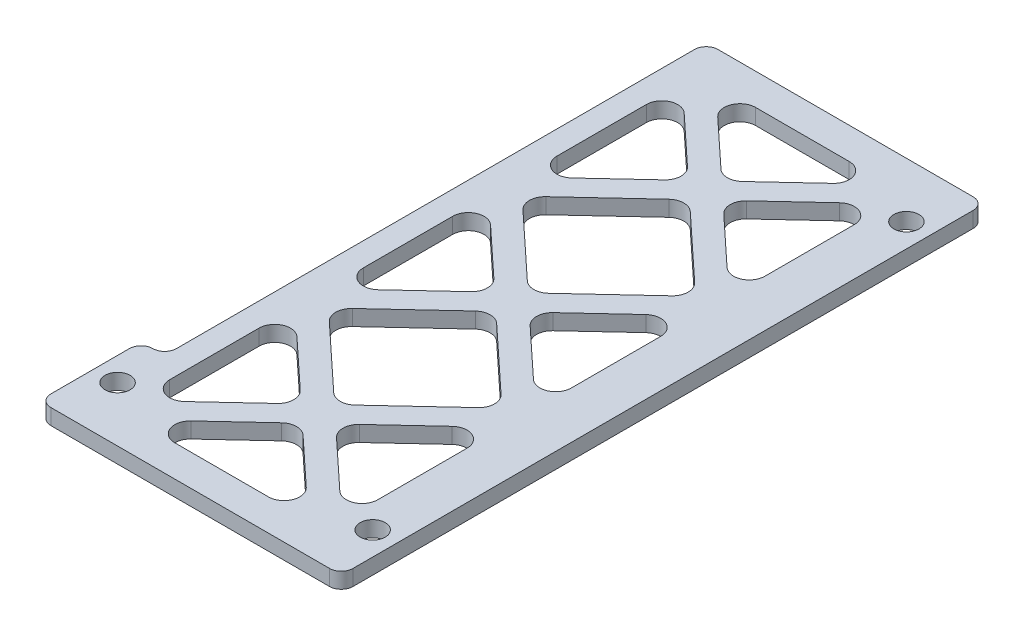
SolidWorks part; units mm, degrees
material "Thornel Mat VMA"
ref_plane "前视基准面" through (0, 0, 0) normal (0, 0, 1) x (1, 0, 0)
ref_plane "上视基准面" through (0, 0, 0) normal (0, 1, 0) x (1, 0, 0)
ref_plane "右视基准面" through (0, 0, 0) normal (1, 0, 0) x (0, 0, -1)
other "Configuration Table"
sketch "草图1" plane through (0, 0, 0) normal (0, 1, 0) x (1, 0, 0)
  line L1 (-19.25, 41) -> (19.25, 41)
  line L2 (-19.25, 41) -> (-19.25, -41)
  line L3 (-19.25, -41) -> (19.25, -41)
  line L4 (19.25, 41) -> (19.25, -41)
  line L5 (-19.25, 41) -> (19.25, -41) construction
  line L6 (-19.25, -41) -> (19.25, 41) construction
  point P0 (0, 0)
  dimension "D1" = 38.5
  dimension "D2" = 82
extrude "凸台-拉伸1" add sketch "草图1" along normal blind 2
sketch "草图2" plane through (0, 0, 0) normal (0, -1, 0) x (1, 0, 0)
  line L0 (19.25, 41) -> (19.25, -41) construction
  line L1 (19.25, -41) -> (-19.25, -41) construction
  line L2 (-19.25, 41) -> (19.25, 41) construction
  line L3 (-19.25, -41) -> (-19.25, 41) construction
  circle A0 centre (16.25, -34) radius 1.6
  circle A1 centre (16.25, 34) radius 1.6
  circle A2 centre (-16.25, 34) radius 1.6
  dimension "D2" = 3.2
  dimension "D1" = 3
  dimension "D3" = 7
  dimension "D4" = 7
  dimension "D5" = 3
extrude "切除-拉伸1" cut sketch "草图2" against normal blind 2
sketch "草图3" plane through (0, 0, 0) normal (0, -1, 0) x (1, 0, 0)
  line L0 (19.25, -41) -> (-19.25, -41) construction
  line L1 (-19.25, -41) -> (-16.25, -41)
  line L2 (-19.25, -41) -> (-19.25, 28)
  line L3 (-19.25, 28) -> (-16.25, 28)
  line L4 (-16.25, -41) -> (-16.25, 28)
  line L5 (-13.25, 37) -> (13.25, 37)
  line L6 (-13.25, 37) -> (-13.25, -37)
  line L7 (-13.25, -37) -> (13.25, -37)
  line L8 (13.25, 37) -> (13.25, -37)
  line L9 (-19.25, 41) -> (19.25, 41) construction
  circle A0 centre (-16.25, 34) radius 1.6 construction
  circle A1 centre (16.25, -34) radius 1.6 construction
  dimension "D1" = 3
  dimension "D2" = 6
  dimension "D3" = 4
  dimension "D4" = 3
  dimension "D5" = 3
  dimension "D6" = 4
extrude "切除-拉伸2" cut sketch "草图3" against normal blind 10
sketch "草图4" plane through (0, 0, 0) normal (0, -1, 0) x (1, 0, 0)
  line L0 (-13.25, 37) -> (13.25, 12.3333)
  line L1 (13.25, -37) -> (13.25, 37) construction
  line L2 (13.25, 37) -> (-13.25, 12.3333)
  line L3 (-13.25, 37) -> (-13.25, -37) construction
  line L4 (-13.25, 12.3333) -> (13.25, -12.3333)
  line L5 (13.25, -12.3333) -> (-13.25, -37)
  line L6 (13.25, 12.3333) -> (-13.25, -12.3333)
  line L7 (-13.25, -12.3333) -> (13.25, -37)
extrude "拉伸-薄壁1" add sketch "草图4" against normal blind 2 thin thin type mid plane wall 3
fillet "圆角1" radius 2 32 edges at (11.0484, 1, 12.3333) (0, 1, 22.6174) (-11.0484, 1, 12.3333) (0, 1, 2.0493) (-11.0484, 1, -12.3333) (0, 1, -22.6174) (11.0484, 1, -12.3333) (0, 1, -2.0493) (-2.2016, 1, -24.6667) (-13.25, 1, -14.3826) (-13.25, 1, -34.9507) (0, 1, 26.7159) (11.0484, 1, 37) (-11.0484, 1, 37) (13.25, 1, 10.2841) (2.2016, 1, 0) (13.25, 1, -10.2841) (-13.25, 1, 14.3826) (-2.2016, 1, 24.6667) (-13.25, 1, 34.9507) (-2.2016, 1, 0) (-13.25, 1, 10.2841) (-13.25, 1, -10.2841) (13.25, 1, -14.3826) (2.2016, 1, -24.6667) (13.25, 1, -34.9507) (13.25, 1, 34.9507) (2.2016, 1, 24.6667) (13.25, 1, 14.3826) (-11.0484, 1, -37) (11.0484, 1, -37) (0, 1, -26.7159)
fillet "圆角2" radius 1.5 6 edges at (-16.25, 1, 28) (19.25, 1, -41) (19.25, 1, 41) (-19.25, 1, 41) (-19.25, 1, 28) (-16.25, 1, -41)
